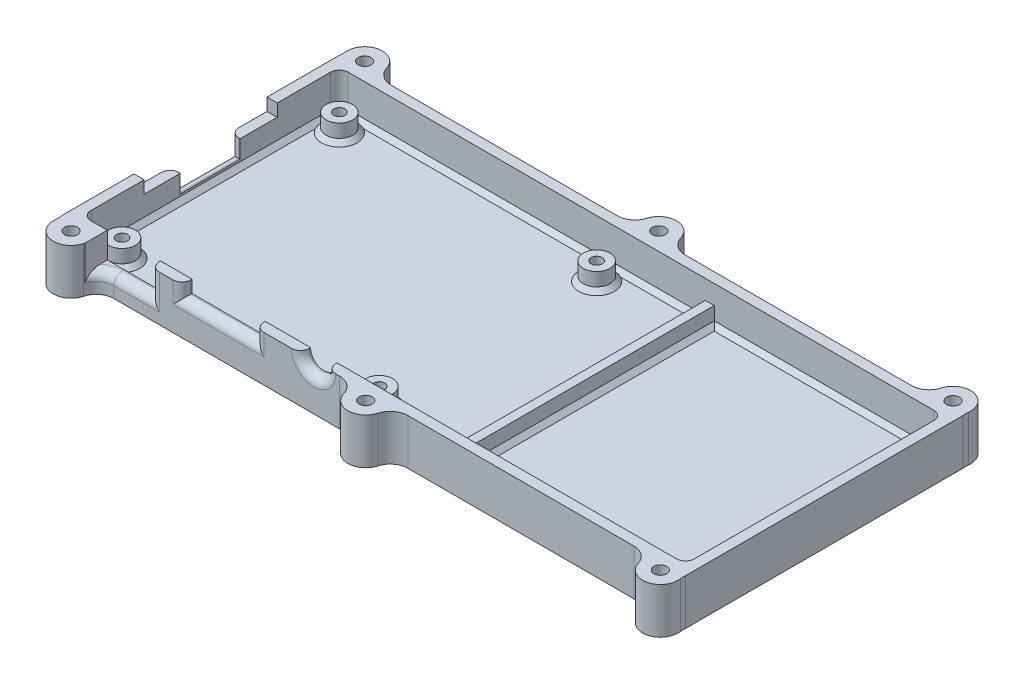
SolidWorks part; units mm, degrees
ref_plane "Front Plane" through (0, 0, 0) normal (0, 0, 1) x (1, 0, 0)
ref_plane "Top Plane" through (0, 0, 0) normal (0, 1, 0) x (1, 0, 0)
ref_plane "Right Plane" through (0, 0, 0) normal (1, 0, 0) x (0, 0, -1)
sketch "Sketch1" plane through (0, 0, 0) normal (0, 1, 0) x (1, 0, 0)
  line L0 (-71.5618, 3.106) -> (62.4382, 3.106) construction
  line L1 (-71.5618, 31.106) -> (62.4382, 31.106)
  line L2 (-71.5618, 31.106) -> (-71.5618, -24.894)
  line L3 (-71.5618, -24.894) -> (62.4382, -24.894)
  line L4 (62.4382, 31.106) -> (62.4382, -24.894)
  line L5 (-60.6618, -24.894) -> (-60.6618, -31.6828) construction
  line L6 (-68.0618, 27.606) -> (-10.0618, 27.606)
  line L7 (-68.0618, 27.606) -> (-68.0618, -21.394)
  line L8 (-68.0618, -21.394) -> (-10.0618, -21.394)
  line L9 (-10.0618, 27.606) -> (-10.0618, -21.394)
  line L10 (-39.5618, -24.894) -> (-39.5618, -31.6828) construction
  line L11 (-18.0618, -24.894) -> (-18.0618, -31.6828) construction
  line L12 (-65.4118, -26.5648) -> (-55.9118, -26.5648) construction
  line L13 (-48.0618, -26.5648) -> (-31.0618, -26.5648) construction
  line L14 (-22.0618, -26.5648) -> (-14.0618, -26.5648) construction
  line L15 (-72.5618, 9.606) -> (-72.5618, -3.394) construction
  line L16 (-71.5618, 3.106) -> (-72.5618, 3.106) construction
  dimension "D1" = 134
  dimension "D2" = 56
  dimension "D3" = 49
  dimension "D4" = 58
  dimension "D5" = 3.5
  dimension "D6" = 3.5
  dimension "D7" = 10.9
  dimension "D8" = 32
  dimension "D9" = 53.5
  dimension "D10" = 2
  dimension "D11" = 13
  dimension "D12" = 9.5
  dimension "D13" = 17
  dimension "D14" = 8
sketch "Sketch3" plane through (0, 0, 0) normal (0, 1, 0) x (1, 0, 0)
  line L4 (65.7382, 34.406) -> (-74.8618, 34.406)
  line L5 (-74.8618, 34.406) -> (-74.8618, -28.194)
  line L6 (-74.8618, -28.194) -> (65.7382, -28.194)
  line L7 (65.7382, -28.194) -> (65.7382, 34.406)
  line L8 (63.4382, 32.106) -> (-72.5618, 32.106)
  line L9 (63.4382, -25.894) -> (63.4382, 32.106)
  line L10 (-72.5618, -25.894) -> (63.4382, -25.894)
  line L11 (-72.5618, 32.106) -> (-72.5618, -25.894)
  line L12 (63.4382, 32.106) -> (-72.5618, 32.106)
  line L13 (63.4382, -25.894) -> (63.4382, 32.106)
  line L14 (-72.5618, -25.894) -> (63.4382, -25.894)
  line L15 (-72.5618, 32.106) -> (-72.5618, -25.894)
  line L16 (-4.5618, 3.106) -> (-4.5618, 34.406) construction
  line L17 (-71.5618, 3.106) -> (62.4382, 3.106) construction
  line L20 (-74.8618, 3.106) -> (65.7382, 3.106) construction
  dimension "D1" = 1
  dimension "D2" = 2.3
extrude "Boss-Extrude1" add sketch "Sketch3" along normal blind 10.3
sketch "Sketch5" plane through (0, 0, 0) normal (0, 1, 0) x (1, 0, 0)
  line L1 (-72.5618, 32.106) -> (63.4382, 32.106)
  line L2 (-72.5618, 32.106) -> (-72.5618, -25.894)
  line L3 (-72.5618, -25.894) -> (63.4382, -25.894)
  line L4 (63.4382, 32.106) -> (63.4382, -25.894)
extrude "Boss-Extrude2" add sketch "Sketch5" along normal blind 2
sketch "Sketch6" plane through (0, 2, 0) normal (0, 1, 0) x (1, 0, 0)
  circle A0 centre (-68.0618, 27.606) radius 3
  circle A1 centre (-68.0618, -21.394) radius 3
  circle A2 centre (-10.0618, -21.394) radius 3
  circle A3 centre (-10.0618, 27.606) radius 3
extrude "Boss-Extrude3" add sketch "Sketch6" along normal blind 4
hole_wizard "Ø2.5 (2.5) Diameter Hole1" positions "Sketch8" profile "Sketch9" hole size "Ø2.5" standard "ANSI Metric"
sketch "Sketch8" plane through (0, 6, 0) normal (0, 1, 0) x (1, 0, 0)
  point P0 (-68.0618, 27.606)
  point P3 (-10.0618, 27.606)
  point P6 (-10.0618, -21.394)
  point P9 (-68.0618, -21.394)
sketch "Sketch9" plane through (-68.0618, 6, -27.606) normal (1, 0, 0) x (0, 0, 1)
  line L0 (0, 0) -> (0, 8.7511)
  line L1 (0, 8.7511) -> (1.25, 8)
  line L2 (1.25, 8) -> (1.25, 0)
  line L5 (1.25, 0) -> (0, 0)
  line L10 (0, 8.7511) -> (-1.25, 8) construction
  line L11 (0, -6.35) -> (0, 107.95) construction
  dimension "Hole Dia." = 2.5
  dimension "Hole Depth" = 8
  dimension "Drill Angle" = 118
sketch "Sketch10" plane through (0, 2, 0) normal (0, 1, 0) x (1, 0, 0)
  line L0 (63.4382, 32.106) -> (-72.5618, 32.106) construction
  line L1 (9.9382, 32.106) -> (11.9382, 32.106)
  line L2 (9.9382, 32.106) -> (9.9382, -25.894)
  line L3 (9.9382, -25.894) -> (11.9382, -25.894)
  line L4 (11.9382, 32.106) -> (11.9382, -25.894)
  line L5 (-72.5618, -25.894) -> (63.4382, -25.894) construction
  line L6 (-10.0618, 27.606) -> (-10.0618, -21.394) construction
  dimension "D1" = 2
  dimension "D2" = 20
extrude "Boss-Extrude4" add sketch "Sketch10" along normal blind 4
sketch "Sketch11" plane through (0, 0, 28.194) normal (0, 0, 1) x (1, 0, 0)
  line L0 (-74.8618, 10.3) -> (-74.8618, 0) construction
  line L1 (-66.8618, 10.3) -> (-54.8618, 10.3)
  line L2 (-66.8618, 10.3) -> (-66.8618, 4.5)
  line L3 (-66.8618, 4.5) -> (-54.8618, 4.5)
  line L4 (-54.8618, 10.3) -> (-54.8618, 4.5)
  line L5 (-74.8618, 0) -> (65.7382, 0) construction
  line L6 (-60.8618, 10.3) -> (-60.6618, 0) construction
  line L7 (-65.4118, 0) -> (-55.9118, 0) construction
  line L9 (-47.778, 10.3) -> (-31.278, 10.3)
  line L10 (-47.778, 10.3) -> (-47.778, 7.5)
  line L11 (-47.778, 7.5) -> (-31.278, 7.5)
  line L12 (-31.278, 10.3) -> (-31.278, 7.5)
  line L13 (-68.0618, 0) -> (-10.0618, 0) construction
  line L14 (-39.5618, 0) -> (-39.528, 10.3) construction
  line L15 (-48.0618, 0) -> (-31.0618, 0) construction
  line L16 (-18.0618, 0) -> (-18.0618, 10.3) construction
  line L17 (-22.0618, 0) -> (-14.0618, 0) construction
  line L18 (-74.8618, 10.3) -> (65.7382, 10.3) construction
  circle A0 centre (-18.0618, 10.3) radius 3
  dimension "D5" = 6
  dimension "D1" = 4.5
  dimension "D2" = 12
  dimension "D3" = 7.5
  dimension "D4" = 16.5
  dimension "D6" = 8
extrude "Cut-Extrude1" cut sketch "Sketch11" against normal up to next
sketch "Sketch12" plane through (-74.8618, 0, 0) normal (-1, 0, 0) x (0, 0, 1)
  line L0 (-3.106, 0) -> (-3.106, 10.3) construction
  line L1 (-27.606, 0) -> (21.394, 0) construction
  line L2 (-34.406, 10.3) -> (28.194, 10.3) construction
  line L4 (-9.7329, 10.3) -> (3.7671, 10.3)
  line L5 (-9.7329, 10.3) -> (-9.7329, 3.5)
  line L6 (-9.7329, 3.5) -> (3.7671, 3.5)
  line L7 (3.7671, 10.3) -> (3.7671, 3.5)
  line L8 (-18.106, 10.3) -> (11.894, 10.3)
  line L9 (-18.106, 10.3) -> (-18.106, 7.5)
  line L10 (-18.106, 7.5) -> (11.894, 7.5)
  line L11 (11.894, 10.3) -> (11.894, 7.5)
  dimension "D1" = 13.5
  dimension "D2" = 3.5
  dimension "D3" = 7.5
  dimension "D4" = 30
extrude "Cut-Extrude2" cut sketch "Sketch12" against normal up to next contours L10 L11 L8 L9 | L7 L6 L5 L4
sketch "Sketch13" plane through (0, 0, 0) normal (0, 1, 0) x (1, 0, 0)
  line L0 (-74.8618, 34.406) -> (-74.8618, 42.3177) construction
  line L1 (65.7382, 34.406) -> (65.7382, 40.5826) construction
  line L2 (-74.8618, 2.9829) -> (65.7382, 3.106) construction
  line L3 (-74.8618, 9.7329) -> (-74.8618, -3.7671) construction
  line L4 (9.9382, 32.106) -> (-72.5618, 32.106) construction
  line L5 (65.7382, -28.194) -> (65.7382, 34.406) construction
  circle A0 centre (-70.8618, 36.106) radius 4
  circle A1 centre (-4.5618, 36.106) radius 4
  circle A2 centre (61.7382, 36.106) radius 4
  circle A3 centre (61.796, -29.901) radius 4
  circle A4 centre (-4.5039, -30.017) radius 4
  circle A5 centre (-70.8038, -30.1331) radius 4
  dimension "D1" = 4
  dimension "D3" = 4
  dimension "D2" = 4
extrude "Boss-Extrude5" add sketch "Sketch13" along normal up to vertex (10.3 mm away) up to point (-15.0618, 10.3, 28.194)
fillet "Fillet2" radius 4 1 edges at (-74.4825, 5.15, -34.406)
fillet "Fillet3" radius 4 8 edges at (58.1785, 5.15, 28.194) (-67.3052, 5.15, 28.194) (-0.9435, 5.15, 28.194) (-8.0643, 5.15, 28.194) (58.1175, 5.15, -34.406) (-0.941, 5.15, -34.406) (-8.1825, 5.15, -34.406) (-67.241, 5.15, -34.406)
fillet "Fillet4" radius 4 3 edges at (-74.3023, 5.15, 28.194) (65.4135, 5.15, 28.194) (65.359, 5.15, -34.406)
hole_wizard "Ø2.9 (2.9) Diameter Hole1" positions "Sketch15" profile "Sketch16" hole size "Ø2.9" standard "ANSI Metric" end condition up to next
sketch "Sketch15" plane through (0, 10.3, 0) normal (0, 1, 0) x (1, 0, 0)
  point P0 (-70.8618, 36.106)
  point P3 (-4.5618, 36.106)
  point P6 (61.7382, 36.106)
  point P9 (61.796, -29.901)
  point P12 (-4.5039, -30.017)
  point P15 (-70.8038, -30.1331)
sketch "Sketch16" plane through (-70.8618, 10.3, -36.106) normal (1, 0, 0) x (0, 0, 1)
  line L0 (0, 0) -> (0, 10.3)
  line L1 (0, 10.3) -> (1.45, 10.3)
  line L2 (1.45, 10.3) -> (1.45, 0)
  line L5 (1.45, 0) -> (0, 0)
  line L11 (0, -6.35) -> (0, 107.95) construction
  dimension "Thru Hole Dia." = 2.9
  dimension "Thru Hole Depth" = 10.3
fillet "Fillet6" radius 2 1 edges at (63.4382, 6.15, -32.106)
fillet "Fillet7" radius 2 1 edges at (63.4382, 6.15, 25.894)
fillet "Fillet8" radius 2 2 edges at (-72.5618, 6.15, 25.894) (-72.5618, 6.15, -32.106)
chamfer "Chamfer1" distance 1 angle 45 4 edges at (-68.0618, 2, 24.394) (-10.0618, 2, 24.394) (-10.0618, 2, -24.606) (-68.0618, 2, -24.606)
chamfer "Chamfer2" distance 1 angle 45 12 edges at (11.9382, 2, -3.106) (36.6882, 2, 25.894) (36.6882, 2, -32.106) (62.8524, 2, 25.3082) (62.8524, 2, -31.5202) (63.4382, 2, -3.106) (-30.3118, 2, 25.894) (-71.976, 2, 25.3082) (-72.5618, 2, -3.106) (-71.976, 2, -31.5202) (9.9382, 2, -3.106) (-30.3118, 2, -32.106)
sketch "Sketch17" plane through (0, 0, 28.194) normal (0, 0, 1) x (1, 0, 0)
  line L0 (-53.9318, 4.5) -> (-63.0738, 4.5) construction
  line L1 (-66.9388, 10.3) -> (-54.9388, 10.3)
  line L2 (-66.9388, 10.3) -> (-66.9388, 4.5)
  line L3 (-66.9388, 4.5) -> (-54.9388, 4.5)
  line L4 (-54.9388, 10.3) -> (-54.9388, 4.5)
  dimension "D1" = 12
fillet "Fillet9" radius 2 10 edges at (-65.404, 4.5, 28.9428) (-74.8618, 5.5, -9.7329) (-74.8618, 3.5, -2.9829) (-74.8618, 5.5, 3.7671) (-18.0618, 7.3, 28.194) (-31.278, 8.9, 28.194) (-47.778, 8.9, 28.194) (-39.528, 7.5, 28.194) (-54.8618, 7.4, 28.194) (-58.9678, 4.5, 28.194)
